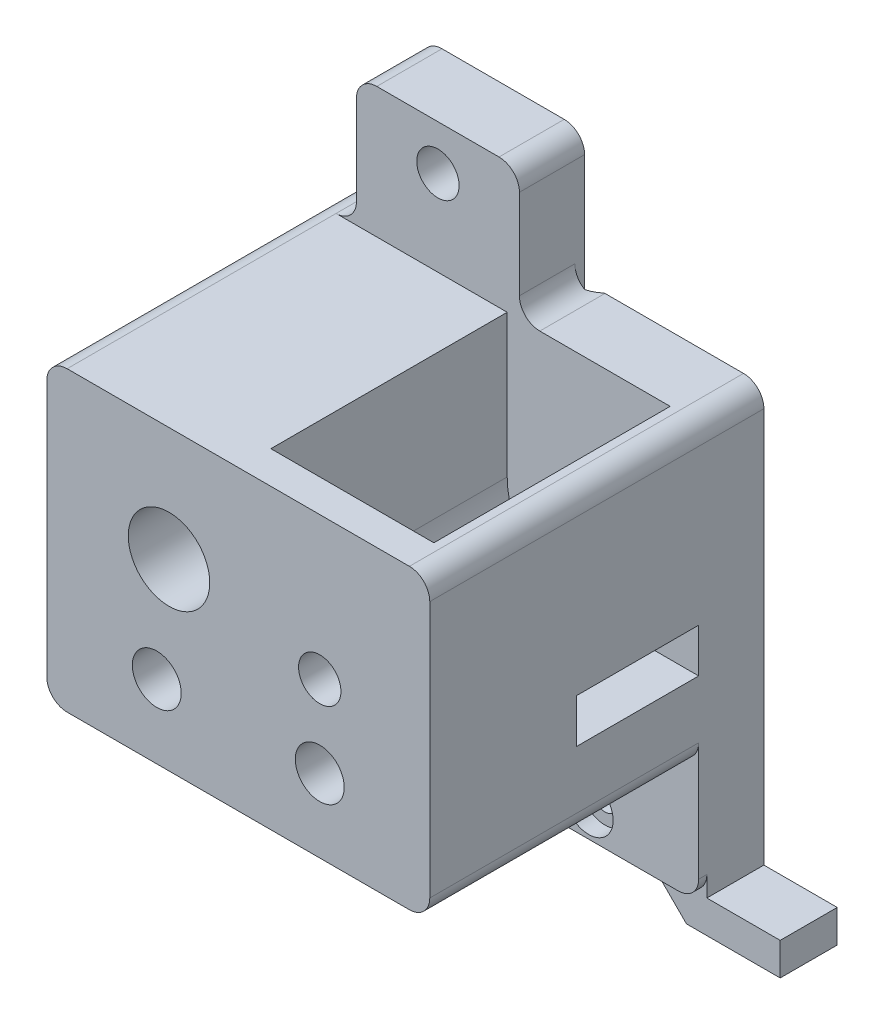
SolidWorks part; units mm, degrees
ref_plane "Спереди" through (0, 0, 0) normal (0, 0, 1) x (1, 0, 0)
ref_plane "Сверху" through (0, 0, 0) normal (0, 1, 0) x (1, 0, 0)
ref_plane "Справа" through (0, 0, 0) normal (1, 0, 0) x (0, 0, -1)
sketch "Эскиз1" plane through (0, 0, 0) normal (0, 0, 1) x (1, 0, 0)
  line L2 (-47, 51) -> (-47, 0)
  line L3 (-47, 0) -> (0, 0)
  line L4 (0, 51) -> (0, 0)
  line L5 (-42, 67) -> (-22, 67)
  line L7 (-42, 73.8692) -> (-42, -49926.1308) construction
  line L8 (-22, 75.542) -> (-22, -49924.458) construction
  line L10 (9.3272, 27) -> (-49990.6728, 27) construction
  line L11 (0, 51) -> (-22, 51)
  line L12 (-22, 51) -> (-22, 67)
  line L13 (-42, 67) -> (-42, 51)
  line L14 (-42, 51) -> (-47, 51)
  dimension "D1" = 47
  dimension "D3" = 20
  dimension "D4" = 5
  dimension "D5" = 51
  dimension "D7" = 67
  dimension "D8" = 27
  dimension "D9" = 40
extrude "Бобышка-Вытянуть1" add sketch "Эскиз1" along normal blind 8
sketch "Эскиз24" plane through (0, 0, 8) normal (0, 0, 1) x (1, 0, 0)
  line L0 (-5.3712, 3.5) -> (7.5116, 3.5) construction
  line L1 (-47, 0) -> (0, 0) construction
  line L2 (0, 0) -> (0, 51) construction
  line L7 (0, 51) -> (-3.5, 51)
  line L8 (0, 0) -> (0, 51) construction
  line L17 (-23.5, 33.5) -> (-23.5, 51)
  line L20 (-3.5, 33.5) -> (-3.5, 51)
  line L21 (-23.5, 51) -> (-47, 51)
  line L22 (-47, 51) -> (-47, 0) construction
  line L23 (-47, 51) -> (-47, 14.5)
  line L24 (-47, 14.5) -> (0, 14.5)
  line L25 (0, 14.5) -> (0, 51)
  line L26 (-22, 51) -> (-22, 67) construction
  line L27 (0, 51) -> (-22, 51) construction
  line L28 (0, 0) -> (0, 51) construction
  circle A0 centre (-13.5, 33.5) radius 9 construction
  arc A2 (-23.5, 33.5) -> (-3.5, 33.5) centre (-13.5, 33.5) ccw
  dimension "D1" = 18
  dimension "D2" = 10
  dimension "D3" = 3.5
  dimension "D4" = 30
  dimension "D5" = 13.5
  dimension "D6" = 14.5
extrude "Бобышка-Вытянуть9" add sketch "Эскиз24" along normal blind 29
sketch "Эскиз25" plane through (0, 0, 37) normal (0, 0, 1) x (1, 0, 0)
  line L8 (-47, 14.5) -> (-47, 51)
  line L9 (-23.5, 51) -> (-47, 51) construction
  line L10 (-47, 51) -> (-47, 14.5) construction
  line L11 (-47, 51) -> (0, 51)
  line L12 (0, 51) -> (0, 14.5)
  line L13 (0, 14.5) -> (-47, 14.5)
extrude "Бобышка-Вытянуть10" add sketch "Эскиз25" along normal blind 4
hole_wizard "Цековка для  болта с шестигранной головкой M51" positions "Трехмерный эскиз1" profile "Эскиз2" counterbore size "M5" standard "ISO" end condition through all
sketch3d "Трехмерный эскиз1"
  point P23 (-33.5, 3.5, 41)
  point P25 (-33.5, 23.5, 41)
  point P27 (-13.5, 3.5, 41)
  point P29 (-13.5, 23.5, 41)
  dimension "D1" = 20
  dimension "D7" = 20
  dimension "D2" = 3.5
  dimension "D3" = 13.5
sketch "Эскиз2" plane through (-33.5, 3.5, 41) normal (1, 0, 0) x (0, -1, 0)
  line L0 (0, 0) -> (0, 41)
  line L1 (0, 41) -> (1.6, 41)
  line L3 (1.6, 41) -> (1.6, 35)
  line L4 (1.6, 35) -> (3, 35)
  line L5 (3, 35) -> (3, 0)
  line L7 (3, 0) -> (0, 0)
  line L11 (0, -6.35) -> (0, 107.95) construction
  dimension "Диаметр сквозного отверстия" = 3.2
  dimension "Глубина сквозного отверстия" = 41
  dimension "Диаметр цековки" = 6
  dimension "Глубина цековки" = 35
sketch "Эскиз22" plane through (0, 0, 0) normal (0, 0, 1) x (1, 0, 0)
  line L2 (-47, 0) -> (0, 0) construction
  line L3 (30.1818, 3.5) -> (-49969.8182, 3.5) construction
  line L4 (43.0826, 23.5) -> (-49956.9174, 23.5) construction
  circle A1 centre (-13.5, 33.5) radius 2.6
  arc A2 (-23.5, 33.5) -> (-16.4661, 23.95) centre (-13.5, 33.5) ccw construction
  dimension "D1" = 5.2
  dimension "D5" = 20
  dimension "D6" = 3.5
extrude "Вырез-Вытянуть9" cut sketch "Эскиз22" along normal through all
sketch "Эскиз23" plane through (0, 0, 0) normal (0, 0, -1) x (-1, 0, 0)
  line L1 (13.5, 38.2343) -> (9.4, 35.8671)
  line L2 (9.4, 35.8671) -> (9.4, 31.1329)
  line L3 (9.4, 31.1329) -> (13.5, 28.7657)
  line L4 (13.5, 28.7657) -> (17.6, 31.1329)
  line L5 (17.6, 31.1329) -> (17.6, 35.8671)
  line L6 (17.6, 35.8671) -> (13.5, 38.2343)
  circle A0 centre (13.5, 33.5) radius 4.1 construction
  dimension "D1" = 8.2
extrude "Вырез-Вытянуть10" cut sketch "Эскиз23" against normal blind 4.2
hole_wizard "Цековка для  болта с шестигранной головкой M52" positions "Трехмерный эскиз2" profile "Эскиз29" counterbore size "M5" standard "ISO" end condition through all
sketch3d "Трехмерный эскиз2"
  point P0 (-32, 61.5, 41)
  point P2 (-32, 37, 41)
  dimension "D1" = 24.5
  dimension "D4" = 5.5
  dimension "D5" = 15
sketch "Эскиз29" plane through (-32, 61.5, 41) normal (1, 0, 0) x (0, -1, 0)
  line L0 (0, 0) -> (0, 41)
  line L1 (0, 41) -> (2.6, 41)
  line L3 (2.6, 41) -> (2.6, 33)
  line L4 (2.6, 33) -> (5, 33)
  line L5 (5, 33) -> (5, 0)
  line L7 (5, 0) -> (0, 0)
  line L11 (0, -6.35) -> (0, 107.95) construction
  dimension "Диаметр сквозного отверстия" = 5.2
  dimension "Глубина сквозного отверстия" = 41
  dimension "Диаметр цековки" = 10
  dimension "Глубина цековки" = 33
sketch "Эскиз30" plane through (0, 51, 0) normal (0, 1, 0) x (1, 0, 0)
  line L0 (-42, 2.7405) -> (-42, -49997.2595) construction
  line L1 (-22, 1.2259) -> (-22, -49998.7741) construction
  line L2 (-47, -8) -> (-47, 0) construction
  line L3 (-42, 0) -> (-42, -1.2)
  line L4 (-42, -1.2) -> (-43.2, -1.2)
  line L5 (-43.2, -1.2) -> (-44.4, 0)
  line L6 (-22, 0) -> (-42, 0) construction
  line L7 (-44.4, 0) -> (-42, 0)
  line L8 (-22, 0) -> (-22, -1.2)
  line L9 (-22, -1.2) -> (-20.8, -1.2)
  line L10 (-20.8, -1.2) -> (-19.6, 0)
  line L11 (-19.6, 0) -> (-22, 0)
  dimension "D1" = 20
  dimension "D2" = 5
  dimension "D3" = 45
  dimension "D4" = 1.2
  dimension "D5" = 1.2
  dimension "D6" = 2.4
  dimension "D7" = 1.2
  dimension "D8" = 1.2
  dimension "D9" = 45
extrude "Вырез-Вытянуть11" cut sketch "Эскиз30" against normal blind 24
fillet "Скругление1" radius 2.5 10 edges at (-47, 0, 4) (-22, 67, 4) (-22, 51, 4.6) (0, 51, 20.5) (0, 0, 4) (-42, 51, 4.6) (-47, 51, 20.5) (-42, 67, 4) (-47, 14.5, 24.5) (0, 14.5, 24.5)
sketch "Эскиз31" plane through (0, 0, 0) normal (0, 0, -1) x (-1, 0, 0)
  line L0 (0, 0) -> (-9, 0)
  line L1 (-9, 0) -> (-9, -4)
  line L2 (-9, -4) -> (2.5, -4)
  line L3 (0, 2.5) -> (0, 48.5) construction
  line L4 (2.5, -4) -> (6.5, 0)
  line L5 (44.5, 0) -> (2.5, 0) construction
  line L6 (0, 2.5) -> (0, 0)
  line L7 (2.5, 0) -> (6.5, 0)
  arc A0 (0, 2.5) -> (2.5, 0) centre (2.5, 2.5) ccw construction
  arc A1 (0, 2.5) -> (2.5, 0) centre (2.5, 2.5) ccw
  dimension "D1" = 9
  dimension "D2" = 4
  dimension "D3" = 45
  dimension "D4" = 4
extrude "Бобышка-Вытянуть11" add sketch "Эскиз31" against normal blind 7
mirror "Зеркальное отражение1" [suppressed] about plane through (0, 0, 0) normal (0, 1, 0) of bodies 132 127
delete or keep bodies "Тело-Удалить/Сохранить 1" [suppressed] type delete bodies bodies 132
sketch "Эскиз32" plane through (0, 0, 0) normal (1, 0, 0) x (0, 0, -1)
  line L1 (-23, 24.1) -> (-8, 24.1)
  line L2 (-23, 24.1) -> (-23, 29.5)
  line L3 (-23, 29.5) -> (-8, 29.5)
  line L4 (-8, 24.1) -> (-8, 29.5)
  line L6 (-7, 0) -> (-8, 0) construction
  line L7 (-8, 2.5) -> (-8, 17) construction
  dimension "D1" = 24.1
  dimension "D2" = 5.4
  dimension "D3" = 15
extrude "Вырез-Вытянуть12" cut sketch "Эскиз32" against normal blind 13.5
sketch "Эскиз33" plane through (-47, 0, 0) normal (-1, 0, 0) x (0, 0, 1)
  line L0 (8, 0) -> (0, 0) construction
  line L1 (37, 29.5) -> (22, 29.5)
  line L2 (37, 29.5) -> (37, 24.1)
  line L3 (37, 24.1) -> (22, 24.1)
  line L4 (22, 29.5) -> (22, 24.1)
  line L5 (37, 33.5) -> (37, 51) construction
  dimension "D1" = 24.1
  dimension "D2" = 5.4
  dimension "D3" = 15
extrude "Вырез-Вытянуть13" cut sketch "Эскиз33" against normal blind 33.5
sketch "Эскиз34" [suppressed] plane through (0, 0, 0) normal (1, 0, 0) x (0, 0, -1)
  line L0 (0, 0) -> (-8, 0) construction
  line L1 (-37, -29.5) -> (-22, -29.5)
  line L2 (-37, -29.5) -> (-37, -24.1)
  line L3 (-37, -24.1) -> (-22, -24.1)
  line L4 (-22, -29.5) -> (-22, -24.1)
  line L7 (-37, -51) -> (-37, -33.5) construction
  dimension "D1" = 5.4
  dimension "D2" = 24.1
  dimension "D3" = 15
extrude "Вырез-Вытянуть14" [suppressed] cut sketch "Эскиз34" against normal blind 13.5
sketch "Эскиз35" [suppressed] plane through (-47, 0, 0) normal (-1, 0, 0) x (0, 0, 1)
  line L0 (8, 0) -> (0, 0) construction
  line L1 (23, -24.1) -> (8, -24.1)
  line L2 (23, -24.1) -> (23, -29.5)
  line L3 (23, -29.5) -> (8, -29.5)
  line L4 (8, -24.1) -> (8, -29.5)
  line L5 (8, -33.5) -> (8, -51) construction
  dimension "D1" = 5.4
  dimension "D2" = 15
  dimension "D3" = 24.1
extrude "Вырез-Вытянуть15" [suppressed] cut sketch "Эскиз35" against normal blind 33.5
